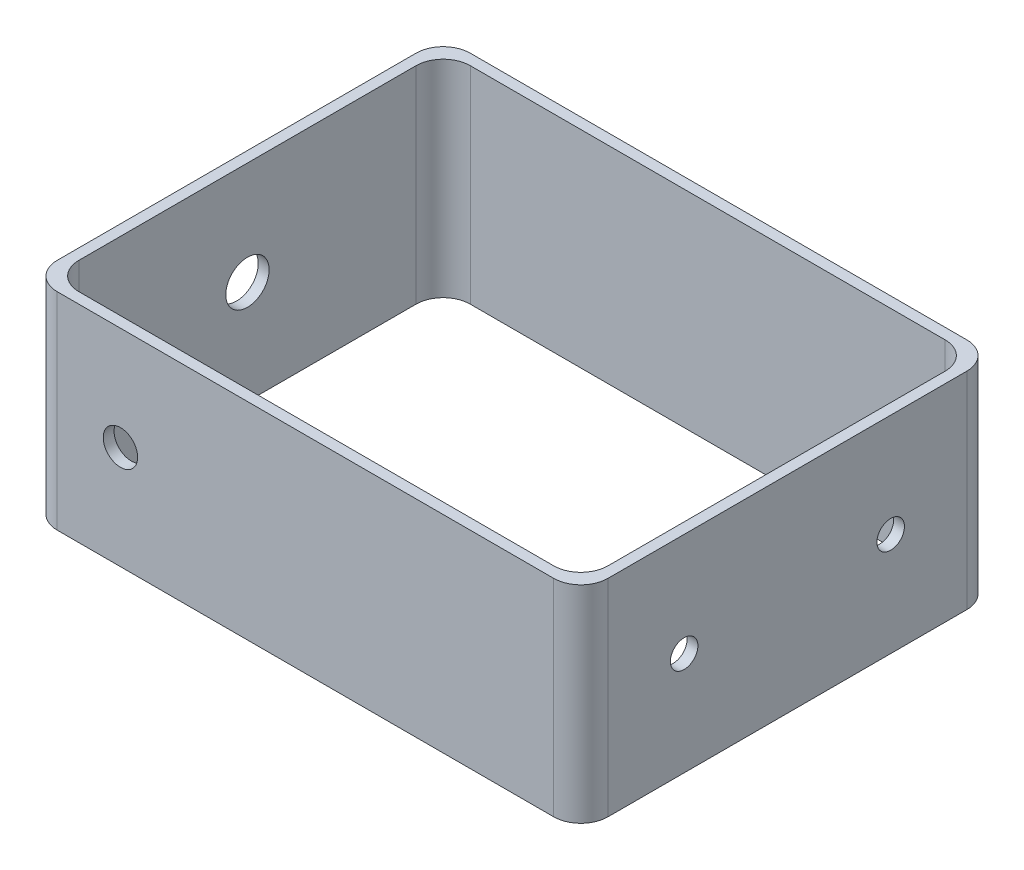
SolidWorks part; units mm, degrees
ref_plane "Front Plane" through (0, 0, 0) normal (0, 0, 1) x (1, 0, 0)
ref_plane "Top Plane" through (0, 0, 0) normal (0, 1, 0) x (1, 0, 0)
ref_plane "Right Plane" through (0, 0, 0) normal (1, 0, 0) x (0, 0, -1)
sketch "Sketch1" plane through (0, 0, 0) normal (0, 1, 0) x (1, 0, 0)
  line L1 (-50.8, 38.1) -> (50.8, 38.1)
  line L2 (-50.8, 38.1) -> (-50.8, -38.1)
  line L3 (-50.8, -38.1) -> (50.8, -38.1)
  line L4 (50.8, 38.1) -> (50.8, -38.1)
  line L5 (-50.8, 38.1) -> (50.8, -38.1) construction
  line L6 (-50.8, -38.1) -> (50.8, 38.1) construction
  point P0 (0, 0)
extrude "Boss-Extrude1" add sketch "Sketch1" along normal blind 38.1
sketch "Sketch3" plane through (0, 38.1, 0) normal (0, 1, 0) x (1, 0, 0)
  line L20 (48.8, -36.1) -> (48.8, 36.1)
  line L21 (-48.8, -36.1) -> (48.8, -36.1)
  line L22 (-48.8, 36.1) -> (-48.8, -36.1)
  line L23 (48.8, 36.1) -> (-48.8, 36.1)
  line L24 (48.8, -36.1) -> (48.8, 36.1)
  line L25 (-48.8, -36.1) -> (48.8, -36.1)
  line L26 (-48.8, 36.1) -> (-48.8, -36.1)
  line L27 (48.8, 36.1) -> (-48.8, 36.1)
  point P0 (0, 0)
  dimension "D1" = 2
extrude "Cut-Extrude1" cut sketch "Sketch3" against normal through all
sketch "Sketch5" plane through (50.8, 0, 0) normal (1, 0, 0) x (0, 0, -1)
  line L0 (0, 0) -> (0, 38.1) construction
  line L1 (-38.1, 0) -> (38.1, 0) construction
  line L2 (-38.1, 38.1) -> (38.1, 38.1) construction
  line L3 (0, 38.1) -> (-38.1, 0) construction
  line L4 (38.1, 0) -> (0, 38.1) construction
  line L5 (0, 0) -> (38.1, 38.1) construction
  line L6 (0, 0) -> (-38.1, 38.1) construction
  point P9 (-19.05, 19.05)
  point P15 (19.05, 19.05)
sketch "Sketch7" plane through (50.8, 0, 0) normal (1, 0, 0) x (0, 0, -1)
  circle A0 centre (-19.05, 19.05) radius 2.54
  circle A1 centre (19.05, 19.05) radius 2.54
extrude "Cut-Extrude2" cut sketch "Sketch7" against normal blind 2
sketch "Sketch9" plane through (-50.8, 0, 0) normal (-1, 0, 0) x (0, 0, 1)
  circle A0 centre (0, 19.05) radius 4
extrude "Cut-Extrude3" cut sketch "Sketch9" against normal blind 2
sketch "Sketch10" plane through (0, 0, 38.1) normal (0, 0, 1) x (1, 0, 0)
  line L0 (-50.8, 19.05) -> (50.8, 19.05) construction
  line L1 (-50.8, 38.1) -> (-50.8, 0) construction
  line L2 (50.8, 38.1) -> (50.8, 0) construction
sketch "Sketch11" plane through (0, 0, 38.1) normal (0, 0, 1) x (1, 0, 0)
  line L0 (-50.8, 19.05) -> (50.8, 19.05) construction
  circle A0 centre (-34.1278, 19.05) radius 3.175
extrude "Cut-Extrude4" cut sketch "Sketch11" against normal blind 2
fillet "Fillet1" radius 5 4 edges at (-50.8, 19.05, 38.1) (-50.8, 19.05, -38.1) (50.8, 19.05, -38.1) (50.8, 19.05, 38.1)
fillet "Fillet2" radius 5 4 edges at (48.8, 19.05, -36.1) (48.8, 19.05, 36.1) (-48.8, 19.05, -36.1) (-48.8, 19.05, 36.1)
sketch "Sketch12" plane through (0, 0, 0) normal (0, -1, 0) x (1, 0, 0)
  text T0 "ΔΣ" font "Century Gothic" height in points 60
extrude "Cut-Extrude5" cut sketch "Sketch12" against normal blind 1 rebuild error yes
